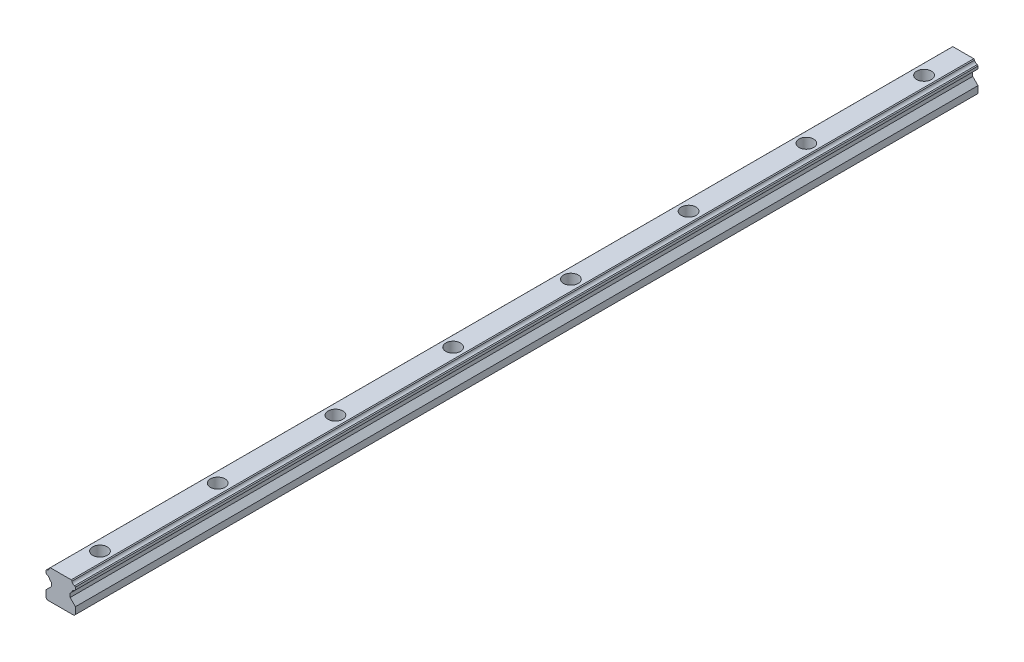
SolidWorks part; units mm, degrees
ref_plane "Front Plane" through (0, 0, 0) normal (0, 0, 1) x (1, 0, 0)
ref_plane "Top Plane" through (0, 0, 0) normal (0, 1, 0) x (1, 0, 0)
ref_plane "Right Plane" through (0, 0, 0) normal (1, 0, 0) x (0, 0, -1)
sketch "Sketch1" plane through (-20, 0, 0) normal (0, 0, 1) x (1, 0, 0)
  line L0 (12.5, 0.7) -> (13.2, 0)
  line L1 (13.2, 0) -> (26.8, 0)
  line L2 (27.5, 4.2) -> (27.5, 0.7)
  line L3 (24.8, 6.9) -> (27.5, 4.2)
  line L4 (24.8, 8.84) -> (24.8, 6.9)
  line L5 (25.7559, 9.7942) -> (24.8, 8.84)
  line L6 (27.5, 11.54) -> (27.0943, 11.1343)
  line L7 (27.5, 12.85) -> (27.5, 11.54)
  line L8 (27.0943, 13.2684) -> (27.5, 12.85)
  line L9 (25.35, 15) -> (25.7559, 14.5941)
  line L10 (27.5, 0.7) -> (26.8, 0)
  line L11 (25.35, 15) -> (14.65, 15)
  line L12 (14.65, 15) -> (14.2441, 14.5941)
  line L13 (12.9057, 13.2684) -> (12.5, 12.85)
  line L14 (12.5, 12.85) -> (12.5, 11.54)
  line L15 (12.5, 11.54) -> (12.9057, 11.1343)
  line L16 (14.2441, 9.7942) -> (15.2, 8.84)
  line L17 (15.2, 8.84) -> (15.2, 6.9)
  line L18 (15.2, 6.9) -> (12.5, 4.2)
  line L19 (12.5, 4.2) -> (12.5, 0.7)
  line L20 (20, 15) -> (20, 0) construction
  arc A0 (27.0943, 11.1343) -> (25.7559, 9.7942) centre (27.3023, 9.5882) ccw
  arc A1 (25.7559, 14.5941) -> (27.0943, 13.2684) centre (27.3003, 14.8148) ccw
  arc A2 (14.2441, 14.5941) -> (12.9057, 13.2684) centre (12.6997, 14.8148) cw
  arc A3 (12.9057, 11.1343) -> (14.2441, 9.7942) centre (12.6977, 9.5882) cw
  dimension "D14" = 1.56
  dimension "D1" = 15
  dimension "D2" = 0.7
  dimension "D3" = 0.7
  dimension "D4" = 4.2
  dimension "D5" = 6.9
  dimension "D6" = 8.84
  dimension "D7" = 4.8
  dimension "D8" = 5.7559
  dimension "D9" = 0.4059
  dimension "D10" = 0.4059
  dimension "D11" = 1.7316
  dimension "D12" = 2.15
  dimension "D13" = 3.46
  dimension "D15" = 7.0943
  dimension "D16" = 3.8657
  dimension "D17" = 5.2058
  dimension "D18" = 15
extrude "Extrude1" add sketch "Sketch1" against normal blind 460
sketch "Sketch2" plane through (0, 0, 0) normal (1, 0, 0) x (0, 0, -1)
  line L0 (20, 15) -> (23.75, 15)
  line L1 (23.75, 15) -> (23.75, 9.7)
  line L2 (23.75, 9.7) -> (22.25, 9.7)
  line L3 (22.25, 9.7) -> (22.25, 0)
  line L4 (22.25, 0) -> (20, 0)
  line L5 (20, 0) -> (20, 15) construction
  line L6 (20, 0) -> (20, 15) construction
  line L7 (20, 15) -> (20, 0)
  line L8 (460, 0) -> (0, 0) construction
  line L9 (460, 15) -> (0, 15) construction
  dimension "D1" = 5.3
  dimension "D2" = 7.5
  dimension "D3" = 4.5
  dimension "D4" = 20
revolve "Cut-Revolve1" cut sketch "Sketch2" angle 360 about L6 reverse direction yes
ref_axis "Axis1" through (0, 0, -168) along (0, 0, 1)
pattern_linear "LPattern1" count 8 spacing 60 along (0, 0, -1) of "Cut-Revolve1"
